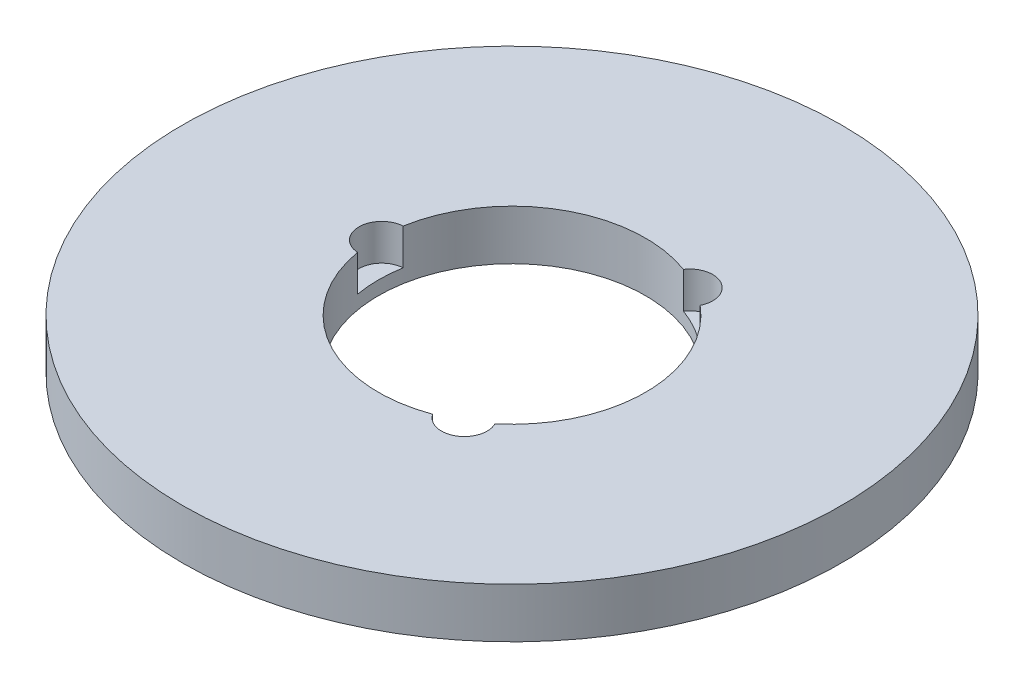
SolidWorks part; units mm, degrees
ref_plane "Front Plane" through (0, 0, 0) normal (0, 0, 1) x (1, 0, 0)
ref_plane "Top Plane" through (0, 0, 0) normal (0, 1, 0) x (1, 0, 0)
ref_plane "Right Plane" through (0, 0, 0) normal (1, 0, 0) x (0, 0, -1)
sketch "Sketch1" plane through (0, 0, 0) normal (0, 1, 0) x (1, 0, 0)
  circle A0 centre (0, 0) radius 92.5
  dimension "FLANGE_OD" = 185
extrude "Boss-Extrude1" add sketch "Sketch1" along normal blind 14
sketch "Sketch2" plane through (0, 0, 0) normal (0, 1, 0) x (1, 0, 0)
  circle A0 centre (0, 0) radius 37.5
  dimension "BORE_D" = 75
extrude "Cut-Extrude1" cut sketch "Sketch2" along normal through all
sketch "Sketch3" plane through (0, 14, 0) normal (0, 1, 0) x (1, 0, 0)
  circle A0 centre (0, 0) radius 36.5474 construction
  circle A1 centre (-36.5474, 0) radius 6.4153
  dimension "BOLT_D" = 12.8307
  dimension "BOLT_PCD" = 73.0949
extrude "Cut-Extrude2" cut sketch "Sketch3" against normal blind 10.1582
pattern_circular "CirPattern1" count 3 over 360 about axis through (0, 0, 0) along (0, 1, 0) of "Cut-Extrude2"
